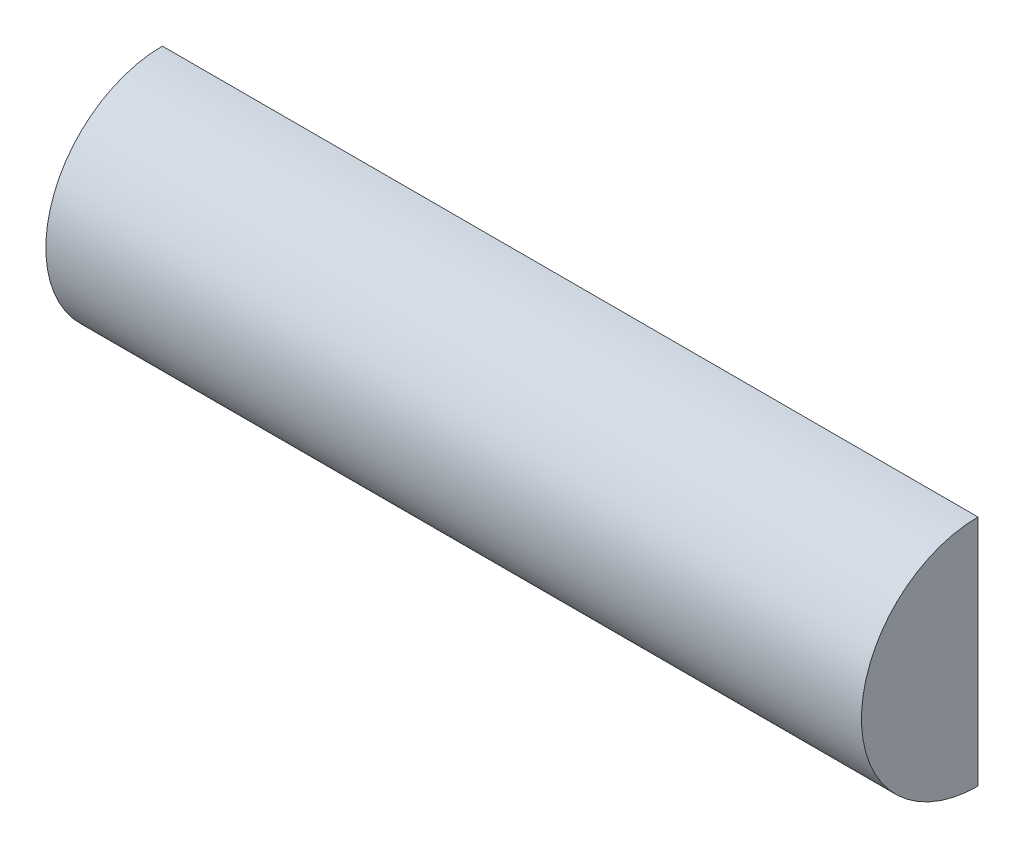
SolidWorks part; units mm, degrees
ref_plane "Front Plane" through (0, 0, 0) normal (0, 0, 1) x (1, 0, 0)
ref_plane "Top Plane" through (0, 0, 0) normal (0, 1, 0) x (1, 0, 0)
ref_plane "Right Plane" through (0, 0, 0) normal (1, 0, 0) x (0, 0, -1)
sketch "Sketch1" plane through (0, 0, 0) normal (0, 0, 1) x (1, 0, 0)
  line L0 (-668.9542, 0) -> (1072.3595, 0) construction
  line L1 (500, 0) -> (500, 40)
  line L2 (500, 40) -> (-350, 40)
  line L3 (-502, 0) -> (500, 0)
  arc A0 (-350, 40) -> (-500, 2.5) centre (-350, -278.75) ccw
  arc A1 (-500, 2.5) -> (-502, 0) centre (-498.093, -1.0756) ccw
  dimension "D1" = 80
  dimension "D2" = 150
  dimension "D3" = 1000
  dimension "D4" = 5
  dimension "D5" = 2
  dimension "D6" = 500
revolve "Forebody" add sketch "Sketch1" angle 180 about L0
sketch "Sketch2" plane through (0, 0, 0) normal (0, 0, 1) x (1, 0, 0)
  line L1 (-10000, 5000) -> (25000, 5000)
  line L2 (-10000, 5000) -> (-10000, 0)
  line L3 (-10000, 0) -> (25000, 0)
  line L4 (25000, 5000) -> (25000, 0)
  dimension "D1" = 5000
  dimension "D2" = 10000
  dimension "D3" = 25000
revolve "Fluid" add sketch "Sketch2" angle 180 about L3
combine bodies "Combine1" operation type subtract main body 103 bodies to subtract 102
sketch "Sketch4" plane through (0, 0, 0) normal (0, 0, 1) x (1, 0, 0)
  line L0 (-622, 0) -> (3000, 0)
  line L1 (3000, 0) -> (3000, 120)
  line L2 (3000, 120) -> (-502, 120)
  line L4 (-502, 0) -> (500, 0) construction
  arc A0 (-502, 120) -> (-622, 0) centre (-502, 0) ccw
  point P6 (0, 0)
  point P7 (0, 0)
  point P9 (-502, 0)
  point P12 (0, 0)
  point P13 (-532.5099, 120)
  point P14 (0, 0)
  point P15 (-502, 0)
  dimension "D2" = 3000
  dimension "D1" = 120
revolve "BOI" add sketch "Sketch4" angle 180 about L0
equation "\"Diameter\"=80"
equation "\"LengthCone\"=57.2246"
equation "\"LengthReference\"=1000"
equation "\"D6@Sketch1\"=\"LengthReference\"/2"
equation "\"D3@Sketch1\"=\"LengthReference\""
equation "\"D1@Sketch1\"=\"Diameter\""
equation "\"radialStream\"= \"LengthReference\" * 5"
equation "\"D1@Sketch2\"=\"radialStream\""
equation "\"lengthUpstream\" = \"LengthReference\" * 10"
equation "\"D2@Sketch2\"=\"lengthUpstream\""
equation "\"lengthDownstream\"= \"LengthReference\" * 25"
equation "\"D3@Sketch2\"=\"lengthDownstream\""
equation "\"radialBOI\"= \"Diameter\" * 1.5"
equation "\"downstreamBOI\"= \"LengthReference\" * 3"
equation "\"D2@Sketch4\"=\"downstreamBOI\""
equation "\"D1@Sketch4\"=\"radialBOI\""
